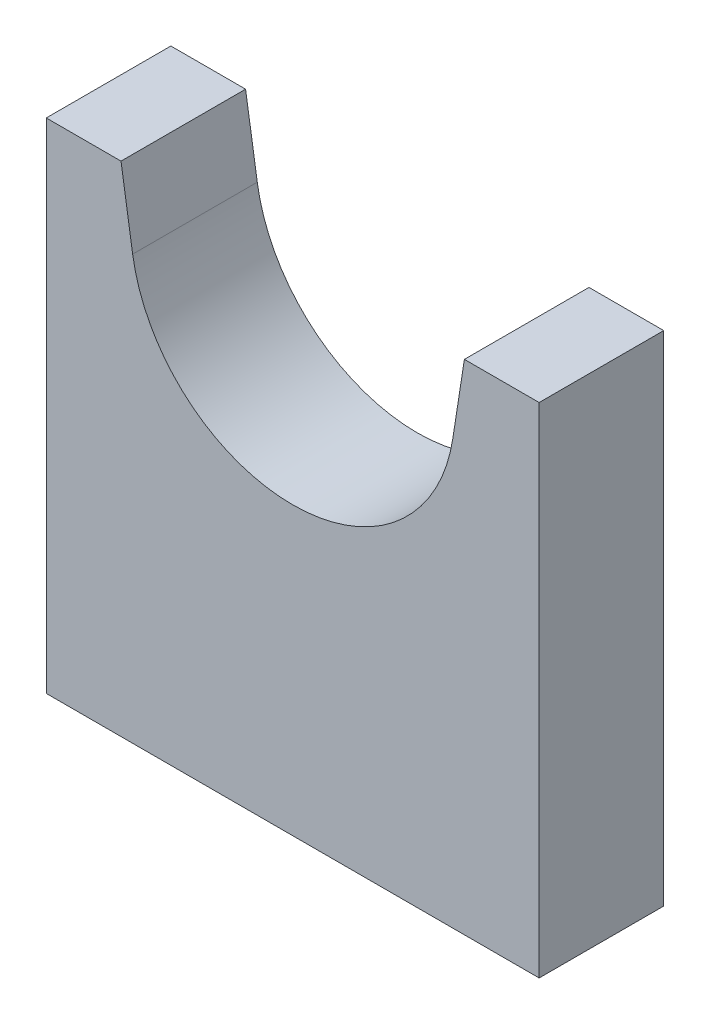
SolidWorks part; units mm, degrees
ref_plane "Front Plane" through (0, 0, 0) normal (0, 0, 1) x (1, 0, 0)
ref_plane "Top Plane" through (0, 0, 0) normal (0, 1, 0) x (1, 0, 0)
ref_plane "Right Plane" through (0, 0, 0) normal (1, 0, 0) x (0, 0, -1)
sketch "Sketch1" plane through (0, 0, 0) normal (0, 0, 1) x (1, 0, 0)
  line L0 (-6.4226, -1) -> (6.4226, -1) construction
  line L1 (-6.4226, -1) -> (-6.8897, 2)
  line L2 (6.4226, -1) -> (6.8897, 2)
  line L3 (-6.8897, 2) -> (-9.8897, 2)
  line L4 (-9.8897, 2) -> (-9.8897, -18)
  line L5 (-9.8897, -18) -> (9.8897, -18)
  line L6 (9.8897, -18) -> (9.8897, 2)
  line L7 (9.8897, 2) -> (6.8897, 2)
  arc A0 (6.4226, -1) -> (-6.4226, -1) centre (0, 0) cw
  point P4 (-179.2333, 25.4)
  dimension "D1" = 6.5
  dimension "D2" = 1
  dimension "D3" = 3
  dimension "D4" = 3
  dimension "D5" = 20
extrude "Boss-Extrude1" add sketch "Sketch1" along normal mid plane 5
